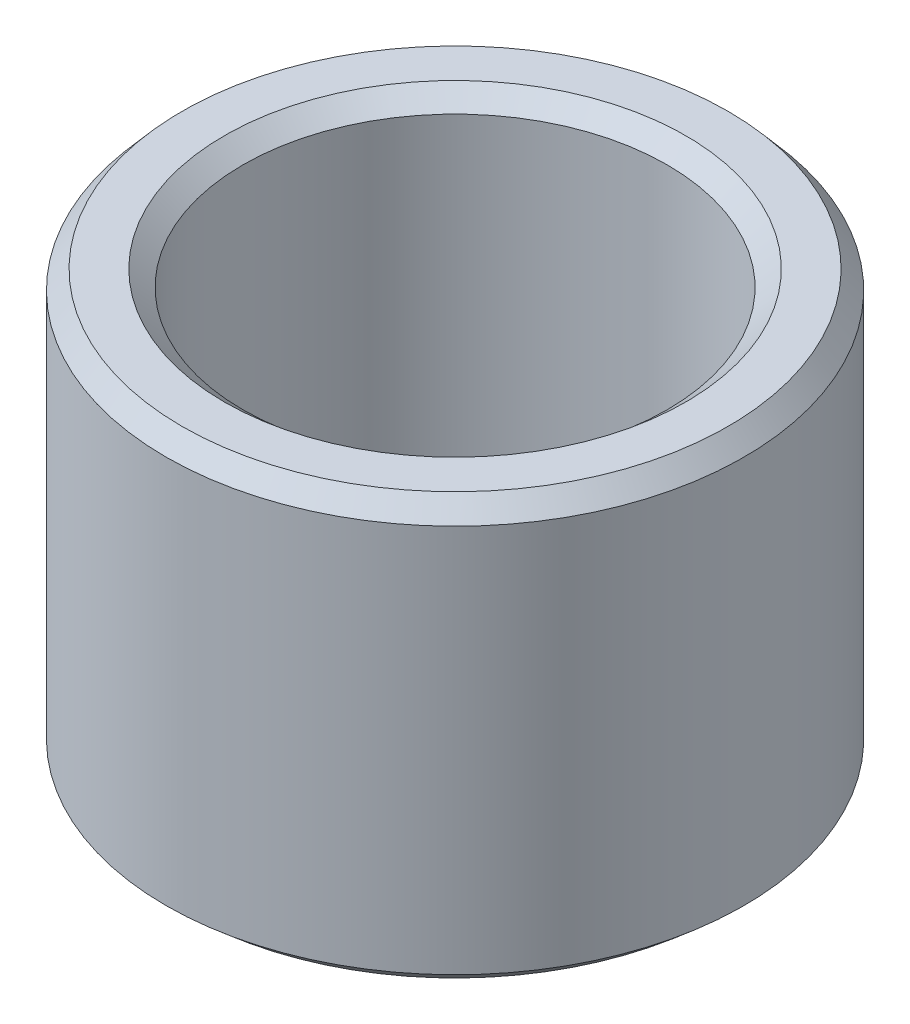
SolidWorks part; units mm, degrees
ref_plane "Front Plane" through (0, 0, 0) normal (0, 0, 1) x (1, 0, 0)
ref_plane "Top Plane" through (0, 0, 0) normal (0, 1, 0) x (1, 0, 0)
ref_plane "Right Plane" through (0, 0, 0) normal (1, 0, 0) x (0, 0, -1)
sketch "Sketch1" plane through (0, 0, 0) normal (0, 1, 0) x (1, 0, 0)
  circle A0 centre (0, 0) radius 55
  dimension "SLEEVE_OD" = 110
extrude "Boss-Extrude1" add sketch "Sketch1" along normal blind 80.5076
sketch "Sketch2" plane through (0, 0, 0) normal (0, 1, 0) x (1, 0, 0)
  circle A0 centre (0, 0) radius 40.3787
  dimension "BORE_D" = 80.7575
extrude "Cut-Extrude1" cut sketch "Sketch2" along normal through all
chamfer "Chamfer1" distance 3.5351 angle 40.706 4 edges at (0, 80.5076, 40.3787) (0, 0, 40.3787) (0, 0, 55) (0, 80.5076, 55) first distance on face at (0, 80.5076, 40.3787) first distance on face at (0, 0, 40.3787) first distance on face at (0, 80.5076, 55)
